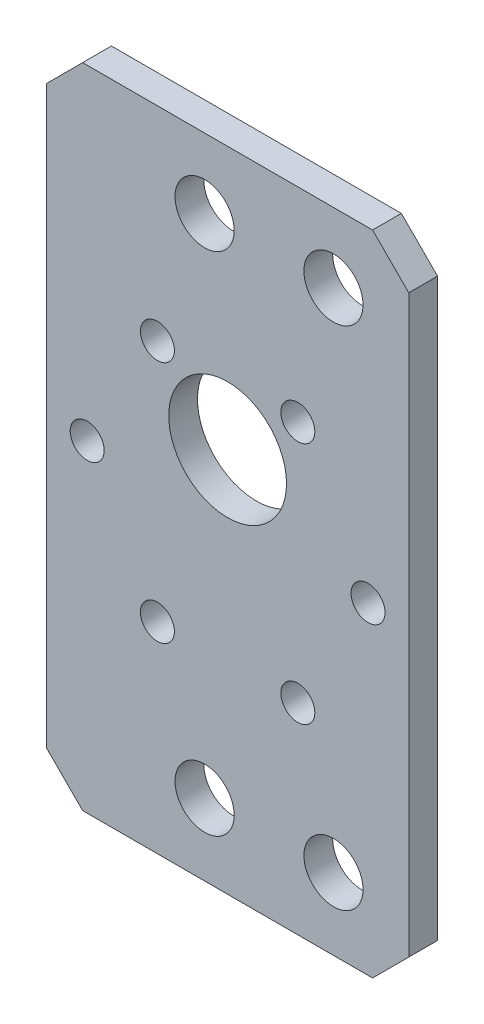
SolidWorks part; units mm, degrees
ref_plane "Front" through (0, 0, 0) normal (0, 0, 1) x (1, 0, 0)
ref_plane "Top" through (0, 0, 0) normal (0, 1, 0) x (1, 0, 0)
ref_plane "Right" through (0, 0, 0) normal (1, 0, 0) x (0, 0, -1)
ref_axis "side-side" through (80.9, 0, 0) along (-1, 0, 0)
ref_axis "up-down" through (0, 50, 0) along (0, -1, 0)
ref_axis "front-back" through (0, 0, -80.9) along (0, 0, 1)
sketch "Sketch1" plane through (0, 0, 0) normal (0, 0, 1) x (1, 0, 0)
  line L0 (0, -42.5) -> (0, 0) construction
  line L1 (-20, 29) -> (20, 29)
  line L2 (-20, 29) -> (-20, -42.5)
  line L3 (-20, -42.5) -> (20, -42.5)
  line L4 (20, 29) -> (20, -42.5)
  circle A0 centre (0, 0) radius 6.5
  circle A1 centre (-7.75, -20.3225) radius 1.25 construction
  circle A2 centre (7.75, 6.5243) radius 1.25 construction
  circle A3 centre (15.5, -6.8991) radius 1.25 construction
  circle A4 centre (7.75, -20.3225) radius 1.25 construction
  circle A5 centre (-15.5, -6.8991) radius 1.25 construction
  circle A6 centre (-7.75, 6.5243) radius 1.25 construction
  circle A7 centre (-7.75, -20.3225) radius 1.25 construction
  circle A8 centre (7.75, 6.5243) radius 1.25 construction
  circle A9 centre (15.5, -6.8991) radius 1.25 construction
  circle A10 centre (7.75, -20.3225) radius 1.25 construction
  circle A11 centre (-15.5, -6.8991) radius 1.25 construction
  circle A12 centre (-7.75, 6.5243) radius 1.25 construction
  dimension "D4" = 13
  dimension "D1" = 40
  dimension "D2" = 42.5
  dimension "D3" = 29
extrude "Boss-Extrude1" add sketch "Sketch1" along normal blind 3.175
chamfer "Chamfer1" distance 4 angle 45 4 edges at (-20, 29, 1.5875) (20, 29, 1.5875) (-20, -42.5, 1.5875) (20, -42.5, 1.5875)
sketch "Sketch2" plane through (0, 0, 3.175) normal (0, 0, 1) x (1, 0, 0)
  circle A0 centre (-7.75, 6.5243) radius 1.875
  circle A1 centre (7.75, 6.5243) radius 1.875
  circle A2 centre (15.5, -6.8991) radius 1.875
  circle A3 centre (7.75, -20.3225) radius 1.875
  circle A4 centre (-7.75, -20.3225) radius 1.875
  circle A5 centre (-15.5, -6.8991) radius 1.875
  dimension "D1" = 3.75
extrude "Cut-Extrude1" cut sketch "Sketch2" against normal through all
hole_wizard "1/4 Clearance Hole1" positions "Sketch3" profile "Sketch4" hole size "1/4" standard "ANSI Inch" end condition through all
sketch "Sketch3" plane through (0, 0, 0) normal (0, 0, -1) x (-1, 0, 0)
  point P0 (-11.684, 21.2996)
  point P3 (2.54, 21.2996)
  point P6 (-11.684, -34.5804)
  point P9 (2.54, -34.5804)
sketch "Sketch4" plane through (11.684, 21.2996, 0) normal (1, 0, 0) x (0, 1, 0)
  line L0 (0, 0) -> (0, 3.175)
  line L1 (0, 3.175) -> (3.2639, 3.175)
  line L2 (3.2639, 3.175) -> (3.2639, 0)
  line L5 (3.2639, 0) -> (0, 0)
  line L11 (0, -6.35) -> (0, 107.95) construction
  dimension "Thru Hole Dia." = 6.5278
  dimension "Thru Hole Depth" = 3.175
